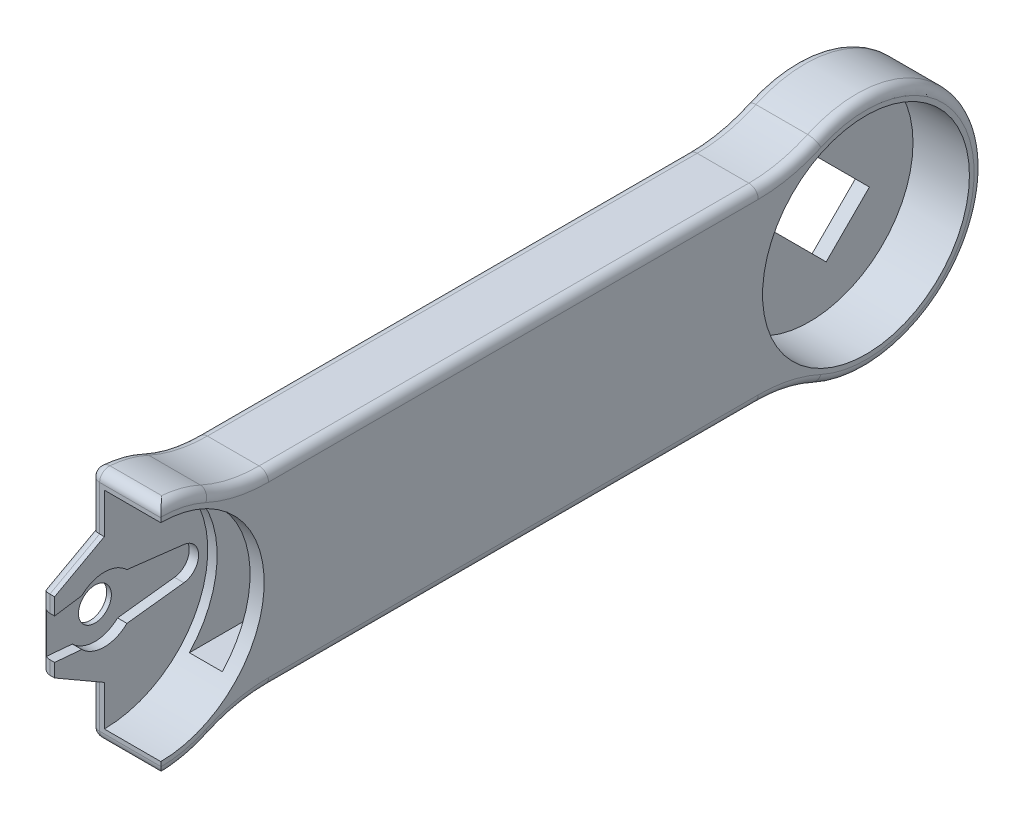
SolidWorks part; units mm, degrees
material "ABS"
ref_plane "Front Plane" through (0, 0, 0) normal (0, 0, 1) x (1, 0, 0)
ref_plane "Top Plane" through (0, 0, 0) normal (0, 1, 0) x (1, 0, 0)
ref_plane "Right Plane" through (0, 0, 0) normal (1, 0, 0) x (0, 0, -1)
sketch "Sketch1" plane through (0, 0, 0) normal (1, 0, 0) x (0, 0, -1)
  line L0 (22.9129, 20) -> (127.0871, 20)
  line L1 (22.9129, -20) -> (127.0871, -20)
  line L2 (-6.684, 0) -> (12.0951, 0) construction
  arc A0 (10.4149, 22.7273) -> (10.4149, -22.7273) centre (0, 0) ccw
  arc A1 (139.5851, -22.7273) -> (139.5851, 22.7273) centre (150, 0) ccw
  arc A2 (22.9129, 20) -> (10.4149, 22.7273) centre (22.9129, 50) cw
  arc A3 (127.0871, 20) -> (139.5851, 22.7273) centre (127.0871, 50) ccw
  arc A4 (127.0871, -20) -> (139.5851, -22.7273) centre (127.0871, -50) cw
  arc A5 (22.9129, -20) -> (10.4149, -22.7273) centre (22.9129, -50) ccw
  point P8 (15, 20)
  point P13 (135, 20)
  dimension "D1" = 50
  dimension "D3" = 40
  dimension "D4" = 30
  dimension "D5" = 30
  dimension "D2" = 120
extrude "Boss-Extrude1" add sketch "Sketch1" along normal blind 15
sketch "Sketch2" plane through (15, 0, 0) normal (1, 0, 0) x (0, 0, -1)
  circle A0 centre (0, 0) radius 22
  arc A1 (10.4149, 22.7273) -> (10.4149, -22.7273) centre (0, 0) ccw construction
  circle A2 centre (150, 0) radius 22
  arc A3 (139.5851, -22.7273) -> (139.5851, 22.7273) centre (150, 0) ccw construction
  dimension "D1" = 3
  dimension "D2" = 3
extrude "Cut-Extrude1" cut sketch "Sketch2" against normal offset from surface (12 mm away) 3 up to face at (0, 0, -75)
sketch "Sketch3" plane through (0, 0, 0) normal (0, 0, 1) x (1, 0, 0)
  line L0 (15, 20) -> (0, 20) construction
  line L1 (5, -15) -> (12, -15)
  line L2 (5, -15) -> (5, 15)
  line L3 (5, 15) -> (12, 15)
  line L4 (12, -15) -> (12, 15)
  line L5 (5, -15) -> (12, 15) construction
  line L6 (5, 15) -> (12, -15) construction
  line L7 (15, -22) -> (15, 22) construction
  line L8 (0, 25) -> (0, -25) construction
  line L9 (15, -20) -> (0, -20) construction
  point P0 (8.5, 0)
  dimension "D1" = 5
  dimension "D2" = 3
  dimension "D3" = 5
  dimension "D4" = 5
extrude "Cut-Extrude2" cut sketch "Sketch3" against normal up to surface (133.9065 mm away) up to face at (15, 0, -172)
sketch "Sketch4" plane through (3, 0, 0) normal (1, 0, 0) x (0, 0, -1)
  line L0 (153.5355, -12.7279) -> (137.2721, 3.5355)
  line L1 (137.2721, 3.5355) -> (146.4645, 12.7279)
  line L2 (146.4645, 12.7279) -> (162.7279, -3.5355)
  line L3 (162.7279, -3.5355) -> (153.5355, -12.7279)
  line L4 (146.4645, 12.7279) -> (153.5355, -12.7279) construction
  line L5 (137.2721, 3.5355) -> (162.7279, -3.5355) construction
  line L6 (150, -14.8808) -> (150, 12.62) construction
  line L7 (137.632, 12.368) -> (160.8855, -10.8855) construction
  point P2 (150, 0)
  dimension "D3" = 45
  dimension "D1" = 23
  dimension "D2" = 13
extrude "Cut-Extrude3" cut sketch "Sketch4" against normal through all both and the other way through all
sketch "Sketch6" plane through (3, 0, 0) normal (1, 0, 0) x (0, 0, -1)
  line L0 (4.807, 4.95) -> (16.9147, 3.5257)
  line L1 (16.9147, -3.5257) -> (4.807, -4.95)
  line L14 (-4.807, -4.95) -> (-16.9531, -3.9022)
  line L16 (-16.8687, 3.1778) -> (-4.807, 4.95)
  line L17 (-4.807, 4.95) -> (4.807, 4.95) construction
  line L18 (-4.807, -4.95) -> (4.807, -4.95) construction
  line L19 (-4.807, 4.95) -> (-4.807, -4.95) construction
  line L20 (4.807, 4.95) -> (4.807, -4.95) construction
  circle A8 centre (0, 0) radius 27 construction
  arc A9 (-4.807, -4.95) -> (4.807, -4.95) centre (0, 0) ccw
  arc A10 (16.9147, 3.5257) -> (16.9147, -3.5257) centre (16.5, 0) cw
  arc A12 (4.807, 4.95) -> (-4.807, 4.95) centre (0, 0) ccw
  arc A24 (-16.9531, -3.9022) -> (-16.8687, 3.1778) centre (-16.648, -0.3653) cw
  dimension "D2" = 16.5
  dimension "D3" = 3.55
  dimension "D1" = 13.8
  dimension "D6" = 13.289
  dimension "D4" = 13.418
extrude "Cut-Extrude4" cut sketch "Sketch6" against normal blind 2
sketch "Sketch7" plane through (3, 0, 0) normal (1, 0, 0) x (0, 0, -1)
  circle A0 centre (0, 0) radius 3.5
  dimension "D1" = 7
extrude "Cut-Extrude5" cut sketch "Sketch7" against normal up to surface (3 mm away) up to face at (0, 0, -150)
sketch "Sketch8" plane through (15, 0, 0) normal (1, 0, 0) x (0, 0, -1)
  line L1 (-17.6978, 26.8453) -> (-37.6375, 26.8453)
  line L2 (-37.6375, 26.8453) -> (-37.6375, -26.8453)
  line L3 (-37.6375, -26.8453) -> (-17.0255, -26.8453)
  line L7 (-10.5827, 7.644) -> (-10.5827, -7.3191)
  line L10 (0, 0) -> (0, -26.8453) construction
  line L11 (-37.6375, 0) -> (0, 0) construction
  line L13 (-4.8758, 26.8453) -> (-17.6978, 26.8453)
  line L15 (-4.8758, -26.8453) -> (-17.0255, -26.8453)
  line L16 (-10.5827, 7.644) -> (0, 13.4227)
  line L17 (0, 13.4227) -> (0, 26.8453)
  line L18 (0, 26.8453) -> (-4.8758, 26.8453)
  line L20 (0, -26.8453) -> (-4.8758, -26.8453)
  line L21 (0, -26.8453) -> (0, -13.4227)
  line L22 (0, -13.4227) -> (-10.5827, -7.3191)
extrude "Cut-Extrude6" cut sketch "Sketch8" against normal through all both and the other way through all
fillet "Fillet1" radius 2 25 edges at (0, -24.4252, -5.33) (0, -20.6897, -16.5169) (0, -20, -75) (0, -20.6897, -133.4831) (0, 0, -175) (0, 20.6897, -133.4831) (0, 24.4252, -5.33) (0, 20.6897, -16.5169) (15, -24.4252, -5.33) (15, -20.6897, -16.5169) (15, -20, -75) (15, -20.6897, -133.4831) (15, 0, -175) (15, 20.6897, -133.4831) (15, 24.4252, -5.33) (15, 20.6897, -16.5169) (0, 0.1625, 10.5827) (0, -19.2113, 0) (0, -10.3709, 5.2914) (0, 10.5333, 5.2914) (0, 19.2113, 0) (0, 20, -75) (15, 20, -75) (7.5, -25, 0) (7.5, 25, 0)
